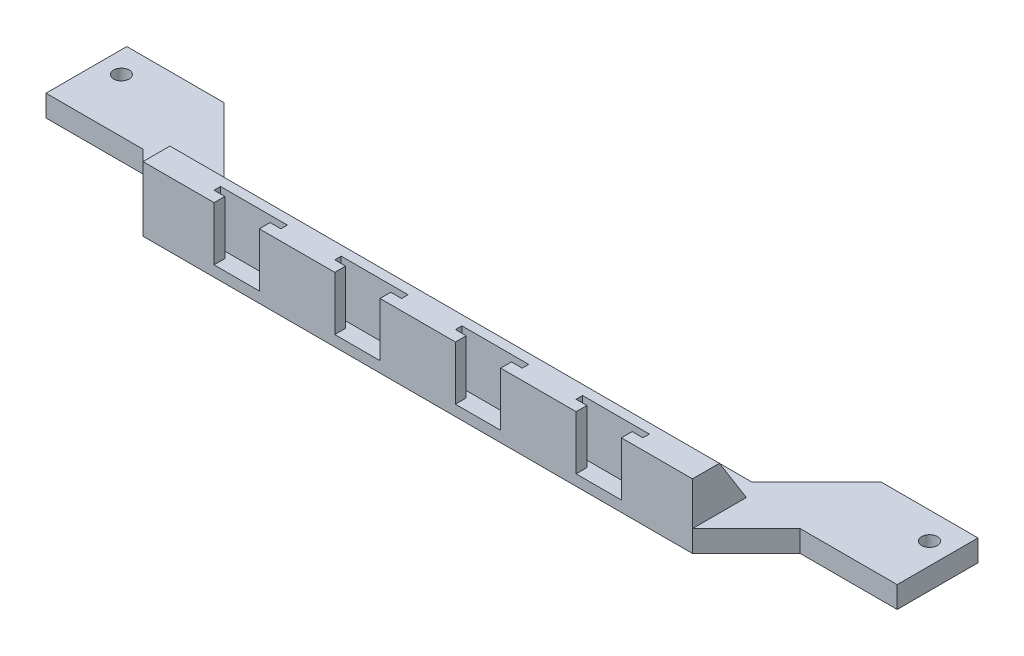
SolidWorks part; units mm, degrees
ref_plane "前视基准面" through (0, 0, 0) normal (0, 0, 1) x (1, 0, 0)
ref_plane "上视基准面" through (0, 0, 0) normal (0, 1, 0) x (1, 0, 0)
ref_plane "右视基准面" through (0, 0, 0) normal (1, 0, 0) x (0, 0, -1)
other "Configuration Table"
sketch "草图1" plane through (0, 0, 0) normal (0, 1, 0) x (1, 0, 0)
  line L1 (80, -12.5) -> (-80, -12.5)
  line L2 (80, -12.5) -> (80, 12.5)
  line L3 (80, 12.5) -> (-80, 12.5)
  line L4 (-80, -12.5) -> (-80, 12.5)
  line L5 (80, -12.5) -> (-80, 12.5) construction
  line L6 (80, 12.5) -> (-80, -12.5) construction
  point P0 (0, 0)
  dimension "D1" = 160
  dimension "D2" = 25
extrude "凸台-拉伸1" add sketch "草图1" along normal blind 4
sketch "草图3" plane through (0, 4, 0) normal (0, 1, 0) x (1, 0, 0)
  line L0 (-80, 12.5) -> (-80, -12.5) construction
  line L1 (80, 12.5) -> (-80, 12.5) construction
  circle A0 centre (-75, 7.5) radius 1.45
  circle A1 centre (75, 7.5) radius 1.45
  dimension "D1" = 5
  dimension "D2" = 150
  dimension "D3" = 2.9
  dimension "D4" = 2.9
  dimension "D5" = 5
  dimension "D6" = 5
extrude "切除-拉伸1" cut sketch "草图3" against normal blind 4
sketch "草图5" plane through (0, 4, 0) normal (0, 1, 0) x (1, 0, 0)
  line L0 (-80, -12.5) -> (80, -12.5) construction
  line L1 (-51, -12.5) -> (51, -12.5)
  line L2 (-51, -12.5) -> (-51, -2.5)
  line L3 (-51, -2.5) -> (51, -2.5)
  line L4 (51, -12.5) -> (51, -2.5)
  line L5 (-80, 12.5) -> (-80, -12.5) construction
  dimension "D1" = 102
  dimension "D2" = 29
  dimension "D3" = 10
extrude "凸台-拉伸2" add sketch "草图5" along normal blind 8
sketch "草图6" plane through (0, 4, 0) normal (0, 1, 0) x (1, 0, 0)
  line L1 (-51, -2.5) -> (-80, -2.5)
  line L2 (-51, -2.5) -> (-51, -12.5)
  line L3 (-51, -12.5) -> (-80, -12.5)
  line L4 (-80, -2.5) -> (-80, -12.5)
  line L5 (51, -2.5) -> (80, -2.5)
  line L6 (51, -2.5) -> (51, -12.5)
  line L7 (51, -12.5) -> (80, -12.5)
  line L8 (80, -2.5) -> (80, -12.5)
extrude "切除-拉伸2" cut sketch "草图6" against normal blind 6
chamfer "倒角1" distance 10 angle 45 2 edges at (51, 2, 2.5) (-51, 2, 2.5)
sketch "草图7" plane through (0, 12, 0) normal (0, 1, 0) x (1, 0, 0)
  line L0 (-51, -2.5) -> (-51, -12.5) construction
  line L1 (-39.8, -9.3) -> (-27.4, -9.3)
  line L2 (-39.8, -9.3) -> (-39.8, -10.5)
  line L3 (-39.8, -10.5) -> (-37.8, -10.5)
  line L4 (-27.4, -9.3) -> (-27.4, -10.5)
  line L5 (-17.4, -9.3) -> (-5, -9.3)
  line L6 (-17.4, -9.3) -> (-17.4, -10.5)
  line L7 (-17.4, -10.5) -> (-15.4, -10.5)
  line L8 (-5, -9.3) -> (-5, -10.5)
  line L9 (5, -9.3) -> (17.4, -9.3)
  line L10 (5, -9.3) -> (5, -10.5)
  line L11 (5, -10.5) -> (7, -10.5)
  line L12 (17.4, -9.3) -> (17.4, -10.5)
  line L13 (27.4, -9.3) -> (39.8, -9.3)
  line L14 (27.4, -9.3) -> (27.4, -10.5)
  line L15 (27.4, -10.5) -> (29.4, -10.5)
  line L16 (39.8, -9.3) -> (39.8, -10.5)
  line L19 (-51, -12.5) -> (51, -12.5) construction
  line L20 (37.8, -10.5) -> (39.8, -10.5)
  line L22 (-37.8, -10.5) -> (-37.8, -12.5)
  line L23 (-37.8, -12.5) -> (-29.4, -12.5)
  line L24 (-29.4, -10.5) -> (-29.4, -12.5)
  line L26 (-15.4, -10.5) -> (-15.4, -12.5)
  line L27 (-15.4, -12.5) -> (-7, -12.5)
  line L28 (-7, -10.5) -> (-7, -12.5)
  line L30 (7, -10.5) -> (7, -12.5)
  line L31 (7, -12.5) -> (15.4, -12.5)
  line L32 (15.4, -10.5) -> (15.4, -12.5)
  line L34 (29.4, -10.5) -> (29.4, -12.5)
  line L35 (29.4, -12.5) -> (37.8, -12.5)
  line L36 (37.8, -10.5) -> (37.8, -12.5)
  line L37 (15.4, -10.5) -> (17.4, -10.5)
  line L38 (-7, -10.5) -> (-5, -10.5)
  line L39 (-29.4, -10.5) -> (-27.4, -10.5)
  dimension "D1" = 11.2
  dimension "D2" = 12.4
  dimension "D3" = 10
  dimension "D4" = 12.4
  dimension "D5" = 10
  dimension "D6" = 12.4
  dimension "D7" = 10
  dimension "D8" = 12.4
  dimension "D9" = 1.2
  dimension "D10" = 1.2
  dimension "D11" = 1.2
  dimension "D12" = 1.2
  dimension "D13" = 2
  dimension "D14" = 2
  dimension "D15" = 2
  dimension "D16" = 2
  dimension "D17" = 2
  dimension "D18" = 2
  dimension "D19" = 2
  dimension "D20" = 2
  dimension "D21" = 2
  dimension "D22" = 2
  dimension "D23" = 2
  dimension "D24" = 2
extrude "切除-拉伸3" cut sketch "草图7" against normal blind 10
sketch "草图9" plane through (-51, 0, 0) normal (-1, 0, 0) x (0, 0, 1)
  line L0 (7.5, 12) -> (2.5, 4)
  line L1 (2.5, 12) -> (12.5, 12) construction
  line L2 (2.5, 4) -> (2.5, 12)
  line L3 (2.5, 12) -> (7.5, 12)
extrude "切除-拉伸4" cut sketch "草图9" against normal blind 142
sketch "草图10" plane through (0, 4, 0) normal (0, 1, 0) x (1, 0, 0)
  line L0 (80, 12.5) -> (-80, 12.5) construction
  line L1 (-61, 12.5) -> (61, 12.5)
  line L2 (-61, 12.5) -> (-61, 0.5)
  line L3 (-61, 0.5) -> (61, 0.5)
  line L4 (61, 12.5) -> (61, 0.5)
  dimension "D1" = 12
extrude "切除-拉伸5" cut sketch "草图10" against normal blind 142
chamfer "倒角2" distance 12 angle 45 2 edges at (-61, 2, -0.5) (61, 2, -0.5)
sketch "草图11" plane through (-80, 0, 0) normal (-1, 0, 0) x (0, 0, 1)
  line L4 (-12.5, 0) -> (2.5, 0)
  line L5 (2.5, 0) -> (2.5, 4)
  line L6 (2.5, 4) -> (-12.5, 4)
  line L7 (-12.5, 4) -> (-12.5, 0)
  line L8 (-12.5, 0) -> (2.5, 0)
  line L9 (2.5, 0) -> (2.5, 4)
  line L10 (2.5, 4) -> (-12.5, 4)
  line L11 (-12.5, 4) -> (-12.5, 0)
  dimension "D1" = 0
extrude "切除-拉伸6" cut sketch "草图11" against normal blind 1
sketch "草图12" plane through (80, 0, 0) normal (1, 0, 0) x (0, 0, -1)
  line L4 (12.5, 4) -> (-2.5, 4)
  line L5 (-2.5, 4) -> (-2.5, 0)
  line L6 (-2.5, 0) -> (12.5, 0)
  line L7 (12.5, 0) -> (12.5, 4)
  line L8 (12.5, 4) -> (-2.5, 4)
  line L9 (-2.5, 4) -> (-2.5, 0)
  line L10 (-2.5, 0) -> (12.5, 0)
  line L11 (12.5, 0) -> (12.5, 4)
  dimension "D1" = 0
extrude "切除-拉伸7" cut sketch "草图12" against normal blind 1
